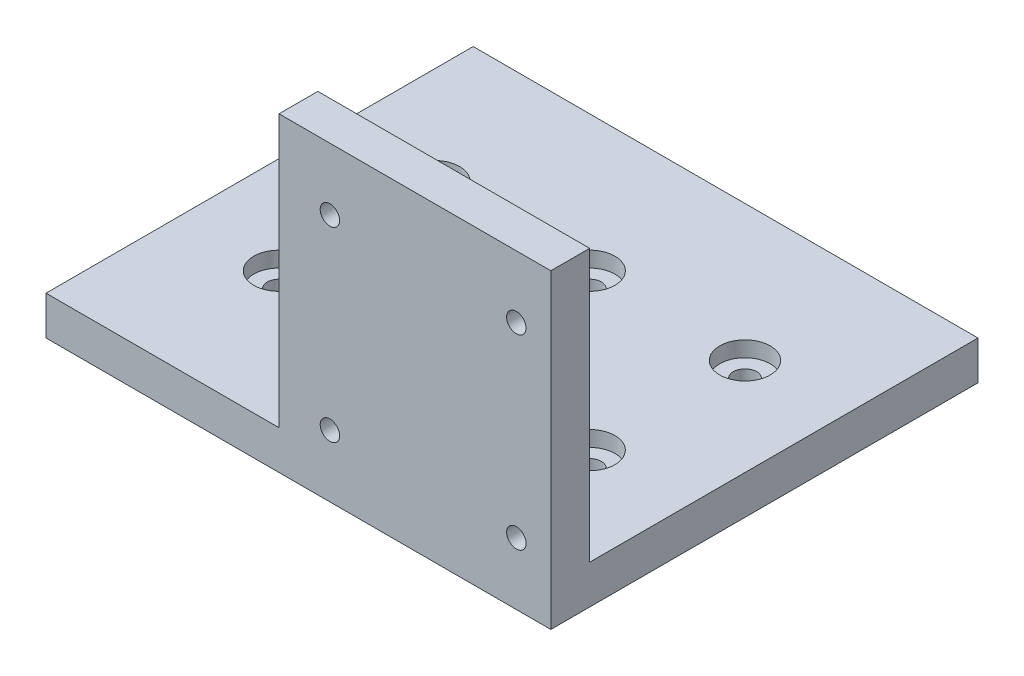
SolidWorks part; units mm, degrees
ref_plane "Front Plane" through (0, 0, 0) normal (0, 0, 1) x (1, 0, 0)
ref_plane "Top Plane" through (0, 0, 0) normal (0, 1, 0) x (1, 0, 0)
ref_plane "Right Plane" through (0, 0, 0) normal (1, 0, 0) x (0, 0, -1)
sketch "Sketch1" plane through (0, 0, 0) normal (0, 1, 0) x (1, 0, 0)
  line L1 (-32.5, -27.5) -> (32.5, -27.5)
  line L2 (-32.5, -27.5) -> (-32.5, 27.5)
  line L3 (-32.5, 27.5) -> (32.5, 27.5)
  line L4 (32.5, -27.5) -> (32.5, 27.5)
  line L5 (-32.5, -27.5) -> (32.5, 27.5) construction
  line L6 (-32.5, 27.5) -> (32.5, -27.5) construction
  point P0 (0, 0)
  dimension "D1" = 55
  dimension "D2" = 65
extrude "Boss-Extrude1" add sketch "Sketch1" along normal blind 5
sketch "Sketch2" plane through (0, 5, 0) normal (0, 1, 0) x (1, 0, 0)
  line L0 (-20, 10) -> (-32.5, 10) construction
  line L1 (-32.5, 27.5) -> (-32.5, -27.5) construction
  line L2 (20, 10) -> (32.5, 10) construction
  line L3 (32.5, -27.5) -> (32.5, 27.5) construction
  line L4 (0, -2.75) -> (0, 2.75) construction
  line L5 (-20, 10) -> (-20, 27.5) construction
  line L6 (32.5, 27.5) -> (-32.5, 27.5) construction
  line L7 (-20, -10) -> (-20, -27.5) construction
  line L8 (-32.5, -27.5) -> (32.5, -27.5) construction
  circle A0 centre (-20, 10) radius 1.5
  circle A1 centre (0, 10) radius 1.5
  circle A2 centre (20, 10) radius 1.5
  circle A3 centre (-20, -10) radius 1.5
  circle A4 centre (0, -10) radius 1.5
  circle A5 centre (20, -10) radius 1.5
  dimension "D1" = 3
  dimension "D2" = 3
  dimension "D4" = 3
  dimension "D6" = 3
  dimension "D8" = 3
  dimension "D9" = 3
  dimension "D3" = 20
  dimension "D5" = 20
  dimension "D7" = 20
extrude "Cut-Extrude1" cut sketch "Sketch2" against normal blind 5
sketch "Sketch3" plane through (0, 5, 0) normal (0, 1, 0) x (1, 0, 0)
  circle A0 centre (-20, 10) radius 3.25
  dimension "D1" = 6.5
extrude "Cut-Extrude2" cut sketch "Sketch3" against normal blind 2
pattern_linear "LPattern1" count 2 spacing 20 along (0, 0, 1) count 3 spacing 20 along (1, 0, 0) of "Cut-Extrude2"
sketch "Sketch5" plane through (0, 5, 0) normal (0, 1, 0) x (1, 0, 0)
  line L0 (32.5, -27.5) -> (32.5, 27.5) construction
  line L1 (-32.5, -27.5) -> (32.5, -27.5)
  line L2 (-32.5, -27.5) -> (-32.5, -22.5)
  line L3 (-32.5, -22.5) -> (32.5, -22.5)
  line L4 (32.5, -27.5) -> (32.5, -22.5)
  line L6 (-18.7014, -27.5) -> (-2.5, -27.5)
  line L7 (-2.5, -27.5) -> (-2.5, -22.5)
  line L8 (-2.5, -22.5) -> (-18.7014, -22.5)
  line M15 (32.5, -27.5) -> (32.5, 27.5)
  line M18 (-32.5, -27.5) -> (32.5, -27.5)
  dimension "D1" = 5
  dimension "D2" = 35
extrude "Boss-Extrude2" add sketch "Sketch5" along normal blind 35 contours L7 L3 M18 M15 region at (15, 5, 25)
sketch "Sketch6" plane through (0, 0, 27.5) normal (0, 0, 1) x (1, 0, 0)
  line L1 (-32.5, 5) -> (-2.5, 5) construction
  circle A0 centre (4.0553, 32) radius 1.25
  circle A1 centre (4.0553, 8) radius 1.25
  circle A2 centre (28.0553, 32) radius 1.25
  circle A3 centre (28.0553, 8) radius 1.25
  point P8 (3.8375, 35.215)
  point P9 (0, 0)
  point P10 (3.4226, 34.0223)
  point P11 (28.0553, 9.7526)
  dimension "D1" = 2.5
  dimension "D2" = 2.5
  dimension "D4" = 2.5
  dimension "D5" = 2.5
  dimension "D3" = 24
  dimension "D6" = 24
  dimension "D7" = 24
  dimension "D8" = 24
  dimension "D9" = 3
extrude "Cut-Extrude3" cut sketch "Sketch6" against normal blind 35
